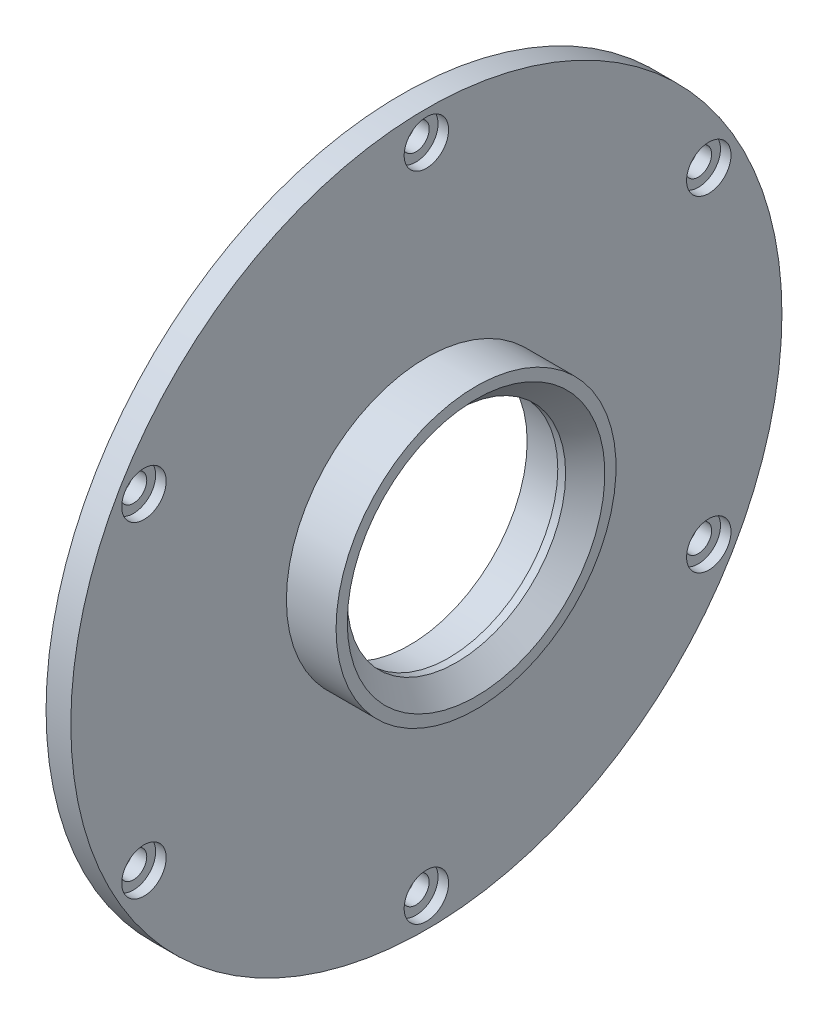
SolidWorks part; units mm, degrees
ref_plane "Front Plane" through (0, 0, 0) normal (0, 0, 1) x (1, 0, 0)
ref_plane "Top Plane" through (0, 0, 0) normal (0, 1, 0) x (1, 0, 0)
ref_plane "Right Plane" through (0, 0, 0) normal (1, 0, 0) x (0, 0, -1)
sketch "Sketch2" plane through (0, 0, 0) normal (0, 0, 1) x (1, 0, 0)
  line L0 (0, 0) -> (58.591, 0) construction
  line L2 (0, 0) -> (18.4, 0)
  line L3 (0, 0) -> (0, 2.5)
  line L4 (0, 2.5) -> (18.4, 2.5)
  line L5 (18.4, 0) -> (18.4, 2.5)
  line L6 (6, 2.5) -> (6, 6)
  line L11 (6, 6) -> (9.97, 6)
  line L16 (12.97, 6) -> (12.97, 3)
  line L17 (12.97, 3) -> (13.6304, 3)
  line L18 (13.6304, 3) -> (13.6304, 2.5)
  line L19 (13.6304, 2.5) -> (6, 2.5)
  line L22 (13.6304, 2.5) -> (16.1104, 2.5)
  line L23 (13.6304, 2.5) -> (13.6304, 4)
  line L24 (13.6304, 4) -> (16.1104, 4)
  line L25 (16.1104, 2.5) -> (16.1104, 4)
  line L27 (6, 6) -> (9.97, 6)
  line L28 (6, 6) -> (6, 9)
  line L29 (6, 9) -> (9.97, 9)
  line L30 (9.97, 6) -> (9.97, 9)
  line L31 (6, 9) -> (6, 8.25)
  line L32 (6, 8.25) -> (5, 8.25)
  line L33 (8.58, 22.001) -> (8.58, 12.476) construction
  line L34 (5, 12.476) -> (12.16, 12.476)
  line L35 (9.97, 9) -> (12.16, 9)
  line L36 (5, 7.5) -> (3, 7.5)
  line L37 (5, 8.25) -> (5, 12.476)
  line L38 (5, 7.5) -> (5, 14)
  line L39 (5, 14) -> (3, 14)
  line L40 (3, 7.5) -> (3, 14)
  line L41 (5, 22.001) -> (12.16, 22.001)
  line L42 (5, 22.001) -> (5, 30.1625)
  line L43 (5, 30.1625) -> (12.16, 30.1625)
  line L44 (12.16, 22.001) -> (12.16, 30.1625)
  line L49 (16.6304, 22.001) -> (16.6304, 7.5)
  line L51 (23.0104, 7.5) -> (23.0104, 6.5)
  line L54 (16.1104, 4) -> (13.6304, 4)
  line L56 (18.0304, 7.5) -> (23.0104, 7.5)
  line L57 (13.16, 22.001) -> (16.6304, 22.001)
  line L58 (16.1104, 3.5) -> (20.0104, 3.5)
  line L59 (29.9004, 14) -> (26.9004, 11)
  line L60 (4, 31.75) -> (18.0304, 31.75)
  line L61 (18.0304, 7.5) -> (23.0104, 7.5)
  line L62 (18.0304, 7.5) -> (18.0304, 12)
  line L63 (18.0304, 12) -> (23.0104, 12)
  line L64 (23.0104, 7.5) -> (23.0104, 12)
  line L65 (18.0304, 31.75) -> (18.0304, 12)
  line L66 (23.0104, 11) -> (26.9004, 11)
  line L67 (34.8004, 23) -> (31.3004, 19.5)
  line L68 (35.8004, 31) -> (38.7904, 33.99)
  line L69 (29.9004, 14) -> (29.9004, 15)
  line L70 (29.9004, 15) -> (22.9304, 15)
  line L71 (22.9304, 15) -> (21.0304, 15)
  line L72 (18.0304, 7.5) -> (16.6304, 7.5)
  line L73 (21.0304, 15) -> (21.0304, 43)
  line L74 (20.0304, 40) -> (10.0704, 40)
  line L75 (10.0704, 40) -> (4, 40)
  line L76 (21.0304, 43) -> (20.0304, 43)
  line L77 (22.9304, 15) -> (29.9004, 15)
  line L78 (22.9304, 15) -> (22.9304, 21)
  line L79 (22.9304, 21) -> (29.9004, 21)
  line L80 (29.9004, 15) -> (29.9004, 21)
  line L81 (10.0704, 40) -> (20.0304, 40)
  line L82 (10.0704, 40) -> (10.0704, 50)
  line L83 (10.0704, 50) -> (20.0304, 50)
  line L84 (20.0304, 40) -> (20.0304, 50)
  line L85 (4, 40) -> (4, 31.75)
  line L86 (12.97, 3) -> (12.97, 2.5)
  line L87 (31.3004, 19.5) -> (29.9004, 19.5)
  line L88 (21.51, 63.5) -> (21.51, 44)
  line L89 (21.51, 63.5) -> (25.9304, 63.5)
  line L90 (25.9304, 63.5) -> (25.9304, 25)
  line L91 (27.8304, 25) -> (25.9304, 25)
  line L92 (10.0704, 48) -> (9, 48)
  line L93 (9, 48) -> (9, 53.476)
  line L94 (9, 53.476) -> (20.0304, 53.476)
  line L95 (20.0304, 53.476) -> (20.0304, 50)
  line L96 (14.5152, 63.001) -> (14.5152, 53.476) construction
  line L97 (9, 63.001) -> (20.0304, 63.001)
  line L98 (9, 63.001) -> (9, 68.2625)
  line L99 (9, 68.2625) -> (20.0304, 68.2625)
  line L100 (20.0304, 63.001) -> (20.0304, 68.2625)
  line L101 (12.97, 6) -> (11.97, 6)
  line L102 (9, 42.5) -> (5, 42.5)
  line L103 (9, 42.5) -> (9, 55)
  line L104 (9, 55) -> (5, 55)
  line L105 (5, 42.5) -> (5, 55)
  line L106 (9.97, 6) -> (10.87, 6)
  line L107 (27.8304, 25) -> (34.8004, 25)
  line L108 (34.8004, 25) -> (34.8004, 23)
  line L109 (0, 0) -> (-2, 0)
  line L110 (0, 0) -> (0, 11)
  line L111 (27.8304, 25) -> (34.8004, 25)
  line L112 (27.8304, 25) -> (27.8304, 32.5)
  line L113 (27.8304, 32.5) -> (34.8004, 32.5)
  line L114 (34.8004, 25) -> (34.8004, 32.5)
  line L115 (35.8004, 31) -> (34.8004, 31)
  line L116 (27.8304, 32.5) -> (27.8304, 64.5)
  line L117 (21.1827, 74.025) -> (6.8477, 74.025)
  line L118 (6.8477, 74.025) -> (6.8477, 76.2)
  line L119 (38.7904, 47.29) -> (30.8304, 55.25)
  line L120 (0, 11) -> (-2, 11)
  line L121 (38.7904, 43.815) -> (30.8529, 43.815)
  line L123 (-4.8, 69.85) -> (1.55, 76.2)
  line L124 (38.7904, 47.29) -> (38.7904, 33.99)
  line L125 (-2, 0) -> (-2, 11)
  line L126 (38.7904, 37.465) -> (30.8529, 37.465)
  line L127 (30.8529, 43.815) -> (30.8529, 37.465)
  line L128 (6, 2.5) -> (6, 0)
  line L129 (0, 63.5) -> (0, 30)
  line L132 (5, 63.5) -> (0, 63.5)
  line L136 (-1.8, 30) -> (-11.76, 30)
  line L138 (-13.76, 25.4) -> (-2, 25.4)
  line L139 (-2, 25.4) -> (-2, 11.5)
  line L140 (27.8304, 64.5) -> (21.1827, 64.5)
  line L141 (-1.8, 30) -> (-11.76, 30)
  line L142 (-1.8, 30) -> (-1.8, 39)
  line L143 (-1.8, 39) -> (-11.76, 39)
  line L144 (-11.76, 30) -> (-11.76, 39)
  line L145 (21.1827, 64.5) -> (21.1827, 74.025)
  line L146 (-12.76, 37) -> (-12.76, 47.29)
  line L147 (-12.76, 37) -> (-11.76, 37)
  line L148 (30.8304, 55.25) -> (30.8304, 76.2)
  line L149 (11.97, 6) -> (11.97, 5.45)
  line L154 (-2, 11.5) -> (1, 11.5)
  line L155 (5, 60.6197) -> (24.05, 60.6197)
  line L160 (5, 60.6197) -> (5, 55.8572)
  line L161 (5, 55.8572) -> (24.05, 55.8572)
  line L166 (24.05, 60.6197) -> (24.05, 55.8572)
  line L167 (5, 60.6197) -> (24.05, 55.8572) construction
  line L172 (5, 55.8572) -> (24.05, 60.6197) construction
  line L173 (24.05, 62.2072) -> (25.9304, 62.2072)
  line L174 (11.97, 5.45) -> (10.87, 5.45)
  line L175 (10.87, 6) -> (10.87, 5.45)
  line L176 (24.05, 62.2072) -> (24.05, 54.2697)
  line L177 (24.05, 54.2697) -> (25.9304, 54.2697)
  line L178 (25.9304, 62.2072) -> (25.9304, 54.2697)
  line L179 (24.05, 62.2072) -> (25.9304, 54.2697) construction
  line L180 (24.05, 54.2697) -> (25.9304, 62.2072) construction
  line L181 (3, 19.6197) -> (15.7, 19.6197)
  line L182 (3, 19.6197) -> (3, 14.8572)
  line L183 (3, 14.8572) -> (15.7, 14.8572)
  line L184 (15.7, 19.6197) -> (15.7, 14.8572)
  line L185 (3, 19.6197) -> (15.7, 14.8572) construction
  line L186 (3, 14.8572) -> (15.7, 19.6197) construction
  line L187 (15.7, 21.2072) -> (16.6304, 21.2072)
  line L188 (15.7, 21.2072) -> (15.7, 13.2697)
  line L189 (15.7, 13.2697) -> (16.6304, 13.2697)
  line L190 (16.6304, 21.2072) -> (16.6304, 13.2697)
  line L191 (15.7, 21.2072) -> (16.6304, 13.2697) construction
  line L192 (15.7, 13.2697) -> (16.6304, 21.2072) construction
  line L193 (1, 11.5) -> (1, 6.5)
  line L194 (1, 6.5) -> (3, 6.5)
  line L195 (23.0104, 6.5) -> (20.0104, 3.5)
  line L196 (5, 63.5) -> (5, 42.5)
  line L197 (5, 42.5) -> (3, 42.5)
  line L198 (3, 42.5) -> (3, 6.5)
  line L199 (6, 0) -> (12.97, 0)
  line L200 (12.97, 0) -> (12.97, 2.5)
  line L201 (18.0304, 31.75) -> (18.0304, 35.875)
  line L202 (18.0304, 35.875) -> (21.0304, 35.875)
  line L203 (30.8304, 76.2) -> (6.8477, 76.2)
  line L204 (3.4027, 69.85) -> (7.8477, 69.85) construction
  line L205 (7.8477, 67.4687) -> (26.8977, 67.4688)
  line L206 (7.8477, 74.025) -> (7.8477, 64.5)
  line L207 (7.8477, 64.5) -> (-1.8, 64.5)
  line L208 (-1.8, 64.5) -> (-1.8, 39)
  line L209 (-12.76, 47.29) -> (-4.8, 55.25)
  line L210 (-4.8, 55.25) -> (-4.8, 69.85)
  line L211 (7.8477, 67.4687) -> (7.8477, 72.2313)
  line L212 (7.8477, 72.2313) -> (26.8977, 72.2313)
  line L213 (26.8977, 67.4688) -> (26.8977, 72.2313)
  line L214 (26.8977, 73.8187) -> (30.8304, 73.8187)
  line L215 (26.8977, 73.8187) -> (26.8977, 65.8813)
  line L216 (26.8977, 65.8813) -> (30.8304, 65.8813)
  line L217 (30.8304, 73.8187) -> (30.8304, 65.8813)
  line L218 (3.4027, 72.2313) -> (25.6277, 72.2313)
  line L219 (3.4027, 72.2313) -> (3.4027, 67.4687)
  line L220 (3.4027, 67.4687) -> (25.6277, 67.4687)
  line L221 (25.6277, 72.2313) -> (25.6277, 67.4687)
  line L222 (25.6277, 69.85) -> (21.1827, 69.85) construction
  line L223 (21.51, 44) -> (22.9304, 44)
  line L224 (22.9304, 44) -> (22.9304, 21)
  line L225 (13.6304, 4) -> (13.6304, 12.2697)
  line L226 (13.6304, 12.2697) -> (13.16, 12.2697)
  line L227 (13.16, 12.2697) -> (13.16, 22.001)
  line L228 (12.16, 9) -> (12.16, 12.476)
  line L229 (-1.8, 30) -> (0, 30)
  line L230 (9, 65.6317) -> (3.4027, 65.6317) construction
  line L231 (20.0304, 65.6317) -> (25.6277, 65.6317) construction
  line L232 (1.55, 76.2) -> (6.8477, 76.2)
  line L233 (-11.76, 30) -> (-13.76, 30)
  line L234 (-13.76, 30) -> (-13.76, 25.4)
  circle A0 centre (26.8804, 25.95) radius 0.95
  circle A1 centre (21.9804, 15.95) radius 0.95
  circle A2 centre (17.3304, 8.2) radius 0.7
  circle A3 centre (10.42, 6.45) radius 0.45
  circle A4 centre (-0.9, 30.9) radius 0.9
  point P7 (24.9902, 58.2385)
  point P131 (16.1652, 17.2385)
  point P135 (14.525, 58.2385)
  point P146 (9.35, 17.2385)
sketch "Sketch3" plane through (0, 0, 0) normal (0, 0, 1) x (1, 0, 0)
  line L0 (34.8004, 25) -> (34.8004, 23) construction
  line L4 (29.9004, 15) -> (29.9004, 21) construction
  line L5 (31.3004, 19.5) -> (29.9004, 19.5) construction
  line L6 (34.8004, 23) -> (31.3004, 19.5) construction
  line L7 (22.9304, 21) -> (29.9004, 21) construction
  line L11 (34.8004, 25) -> (34.8004, 23)
  line L15 (29.9004, 19.5) -> (29.9004, 21)
  line L16 (31.3004, 19.5) -> (29.9004, 19.5)
  line L17 (34.8004, 23) -> (31.3004, 19.5)
  line L18 (22.9304, 21) -> (29.9004, 21)
  line L22 (27.8304, 25) -> (25.9304, 25) construction
  line L23 (27.8304, 25) -> (34.8004, 25) construction
  line L24 (25.9304, 63.5) -> (25.9304, 25) construction
  line L25 (22.9304, 44) -> (22.9304, 21) construction
  line L26 (21.51, 44) -> (22.9304, 44) construction
  line L27 (21.51, 63.5) -> (21.51, 44) construction
  line L28 (21.51, 63.5) -> (25.9304, 63.5) construction
  line L29 (27.8304, 25) -> (25.9304, 25)
  line L30 (27.8304, 25) -> (34.8004, 25)
  line L31 (25.9304, 63.5) -> (25.9304, 25)
  line L32 (22.9304, 44) -> (22.9304, 21)
  line L33 (21.51, 44) -> (22.9304, 44)
  line L34 (21.51, 63.5) -> (21.51, 44)
  line L35 (21.51, 63.5) -> (25.9304, 63.5)
revolve "Revolve1" add sketch "Sketch3" angle 360 about L0
sketch "Sketch4" plane through (0, 0, 0) normal (1, 0, 0) x (0, 0, -1)
  line L0 (0, 0) -> (0, 69.85) construction
  line L1 (0, 0) -> (13.6271, 68.5079) construction
  line L2 (0, 0) -> (0, 58.2385) construction
  line L3 (0, 0) -> (50.436, 29.1192) construction
  line L4 (0, 0) -> (0, 31.75) construction
  line L5 (0, 0) -> (12.1502, 29.3332) construction
  line L6 (0, 0) -> (0, 17.2385) construction
  line L7 (0, 0) -> (14.929, 8.6192) construction
  line L8 (0, 0) -> (0, 58.2385) construction
  line L9 (0, 0) -> (50.436, 29.1192) construction
  line L10 (0, 0) -> (5.9583, 29.9542) construction
  line L11 (0, 0) -> (16.9677, 25.394) construction
  circle A0 centre (0, 0) radius 69.85 construction
  circle A1 centre (0, 0) radius 58.2385 construction
  circle A2 centre (0, 0) radius 31.75 construction
  circle A3 centre (0, 0) radius 17.2385 construction
  circle A4 centre (0, 69.85) radius 3.175
  circle A5 centre (0, 58.2385) radius 4.7625
  circle A6 centre (0, 31.75) radius 3.175
  circle A7 centre (0, 17.2385) radius 4.7625
  circle A8 centre (13.6271, 68.5079) radius 3.175
  circle A9 centre (26.7304, 64.533) radius 3.175
  circle A10 centre (38.8066, 58.0782) radius 3.175
  circle A11 centre (49.3914, 49.3914) radius 3.175
  circle A12 centre (58.0782, 38.8066) radius 3.175
  circle A13 centre (64.533, 26.7304) radius 3.175
  circle A14 centre (68.5079, 13.6271) radius 3.175
  circle A15 centre (69.85, 0) radius 3.175
  circle A16 centre (68.5079, -13.6271) radius 3.175
  circle A17 centre (64.533, -26.7304) radius 3.175
  circle A18 centre (58.0782, -38.8066) radius 3.175
  circle A19 centre (49.3914, -49.3914) radius 3.175
  circle A20 centre (38.8066, -58.0782) radius 3.175
  circle A21 centre (26.7304, -64.533) radius 3.175
  circle A22 centre (13.6271, -68.5079) radius 3.175
  circle A23 centre (0, -69.85) radius 3.175
  circle A24 centre (-13.6271, -68.5079) radius 3.175
  circle A25 centre (-26.7304, -64.533) radius 3.175
  circle A26 centre (-38.8066, -58.0782) radius 3.175
  circle A27 centre (-49.3914, -49.3914) radius 3.175
  circle A28 centre (-58.0782, -38.8066) radius 3.175
  circle A29 centre (-64.533, -26.7304) radius 3.175
  circle A30 centre (-68.5079, -13.6271) radius 3.175
  circle A31 centre (-69.85, 0) radius 3.175
  circle A32 centre (-68.5079, 13.6271) radius 3.175
  circle A33 centre (-64.533, 26.7304) radius 3.175
  circle A34 centre (-58.0782, 38.8066) radius 3.175
  circle A35 centre (-49.3914, 49.3914) radius 3.175
  circle A36 centre (-38.8066, 58.0782) radius 3.175
  circle A37 centre (-26.7304, 64.533) radius 3.175
  circle A38 centre (-13.6271, 68.5079) radius 3.175
  circle A47 centre (50.436, 29.1192) radius 4.7625
  circle A48 centre (50.436, -29.1192) radius 4.7625
  circle A49 centre (0, -58.2385) radius 4.7625
  circle A50 centre (-50.436, -29.1192) radius 4.7625
  circle A51 centre (-50.436, 29.1192) radius 4.7625
  circle A58 centre (12.1502, 29.3332) radius 3.175
  circle A59 centre (22.4506, 22.4506) radius 3.175
  circle A60 centre (29.3332, 12.1502) radius 3.175
  circle A61 centre (31.75, 0) radius 3.175
  circle A62 centre (29.3332, -12.1502) radius 3.175
  circle A63 centre (22.4506, -22.4506) radius 3.175
  circle A64 centre (12.1502, -29.3332) radius 3.175
  circle A65 centre (0, -31.75) radius 3.175
  circle A66 centre (-12.1502, -29.3332) radius 3.175
  circle A67 centre (-22.4506, -22.4506) radius 3.175
  circle A68 centre (-29.3332, -12.1502) radius 3.175
  circle A69 centre (-31.75, 0) radius 3.175
  circle A70 centre (-29.3332, 12.1502) radius 3.175
  circle A71 centre (-22.4506, 22.4506) radius 3.175
  circle A72 centre (14.929, 8.6192) radius 4.7625
  circle A73 centre (14.929, -8.6192) radius 4.7625
  circle A74 centre (0, -17.2385) radius 4.7625
  circle A75 centre (-14.929, -8.6192) radius 4.7625
  circle A76 centre (-14.929, 8.6192) radius 4.7625
  circle A77 centre (0, 0) radius 50
  circle A78 centre (0, 0) radius 9
  circle A79 centre (-12.1502, 29.3332) radius 3.175
  circle A80 centre (0, 0) radius 76.2
  circle A81 centre (0, 0) radius 74.025
  circle A82 centre (0, 69.85) radius 3.9687
  circle A83 centre (49.3914, 49.3914) radius 3.9687
  circle A84 centre (69.85, 0) radius 3.9688
  circle A85 centre (49.3914, -49.3914) radius 3.9687
  circle A86 centre (0, -69.85) radius 3.9687
  circle A87 centre (-49.3914, -49.3914) radius 3.9687
  circle A88 centre (-69.85, 0) radius 3.9688
  circle A89 centre (-49.3914, 49.3914) radius 3.9687
  circle A90 centre (0, 69.85) radius 2.3812
  circle A91 centre (13.6271, 68.5079) radius 2.3812
  circle A92 centre (26.7304, 64.533) radius 2.3813
  circle A93 centre (38.8066, 58.0782) radius 2.3812
  circle A94 centre (49.3914, 49.3914) radius 2.3812
  circle A95 centre (58.0782, 38.8066) radius 2.3812
  circle A96 centre (64.533, 26.7304) radius 2.3813
  circle A97 centre (68.5079, 13.6271) radius 2.3813
  circle A98 centre (69.85, 0) radius 2.3813
  circle A99 centre (68.5079, -13.6271) radius 2.3813
  circle A100 centre (64.533, -26.7304) radius 2.3813
  circle A101 centre (58.0782, -38.8066) radius 2.3812
  circle A102 centre (49.3914, -49.3914) radius 2.3812
  circle A103 centre (38.8066, -58.0782) radius 2.3812
  circle A104 centre (26.7304, -64.533) radius 2.3813
  circle A105 centre (13.6271, -68.5079) radius 2.3812
  circle A106 centre (0, -69.85) radius 2.3812
  circle A107 centre (-13.6271, -68.5079) radius 2.3812
  circle A108 centre (-26.7304, -64.533) radius 2.3813
  circle A109 centre (-38.8066, -58.0782) radius 2.3812
  circle A110 centre (-49.3914, -49.3914) radius 2.3812
  circle A111 centre (-58.0782, -38.8066) radius 2.3812
  circle A112 centre (-64.533, -26.7304) radius 2.3812
  arc A113 (3.0399, 30.8338) -> (8.9911, 29.65) centre (5.9583, 29.9542) cw
  arc A114 (14.6081, 27.3234) -> (19.6532, 23.9523) centre (16.9677, 25.394) cw
  arc A115 (23.9523, 19.6532) -> (27.3234, 14.6081) centre (25.394, 16.9677) cw
  arc A116 (29.65, 8.9911) -> (30.8338, 3.0399) centre (29.9542, 5.9583) cw
  arc A117 (30.8338, -3.0399) -> (29.65, -8.9911) centre (29.9542, -5.9583) cw
  arc A118 (27.3234, -14.6081) -> (23.9523, -19.6532) centre (25.394, -16.9677) cw
  arc A119 (19.6532, -23.9523) -> (14.6081, -27.3234) centre (16.9677, -25.394) cw
  arc A120 (8.9911, -29.65) -> (3.0399, -30.8338) centre (5.9583, -29.9542) cw
  arc A121 (-3.0399, -30.8338) -> (-8.9911, -29.65) centre (-5.9583, -29.9542) cw
  arc A122 (-14.6081, -27.3234) -> (-19.6532, -23.9523) centre (-16.9677, -25.394) cw
  arc A123 (-23.9523, -19.6532) -> (-27.3234, -14.6081) centre (-25.394, -16.9677) cw
  arc A124 (-29.65, -8.9911) -> (-30.8338, -3.0399) centre (-29.9542, -5.9583) cw
  arc A125 (-30.8338, 3.0399) -> (-29.65, 8.9911) centre (-29.9542, 5.9583) cw
  arc A126 (-27.3234, 14.6081) -> (-23.9523, 19.6532) centre (-25.394, 16.9677) cw
  arc A127 (-19.6532, 23.9523) -> (-14.6081, 27.3234) centre (-16.9677, 25.394) cw
  arc A128 (-8.9911, 29.65) -> (-3.0399, 30.8338) centre (-5.9583, 29.9542) cw
  arc A129 (26.9875, 0) -> (26.9932, 0.1932) centre (30.2705, 0) cw
  arc A130 (65.0988, 0.2771) -> (65.0875, 0) centre (68.4964, 0) ccw
  circle A131 centre (1.5875, 0) radius 40
  circle A132 centre (1.5875, 0) radius 2.5
  circle A133 centre (1.5875, 0) radius 3
  circle A134 centre (1.5875, 0) radius 43
  circle A135 centre (-68.5079, -13.6271) radius 2.3813
  circle A136 centre (-69.85, 0) radius 2.3813
  circle A137 centre (-68.5079, 13.6271) radius 2.3813
  circle A138 centre (-64.533, 26.7304) radius 2.3812
  circle A139 centre (-58.0782, 38.8066) radius 2.3812
  circle A140 centre (-49.3914, 49.3914) radius 2.3812
  circle A141 centre (-38.8066, 58.0782) radius 2.3812
  circle A142 centre (-26.7304, 64.533) radius 2.3813
  circle A143 centre (-13.6271, 68.5079) radius 2.3812
  circle A144 centre (0, 58.2385) radius 2.3812
  circle A145 centre (0, 58.2385) radius 3.9688
  circle A146 centre (50.436, 29.1192) radius 3.9688
  circle A147 centre (50.436, 29.1192) radius 2.3813
  circle A148 centre (50.436, -29.1192) radius 3.9687
  circle A149 centre (50.436, -29.1192) radius 2.3812
  circle A150 centre (0, -58.2385) radius 3.9687
  circle A151 centre (0, -58.2385) radius 2.3812
  circle A152 centre (-50.436, -29.1192) radius 3.9687
  circle A153 centre (-50.436, -29.1192) radius 2.3812
  circle A154 centre (-50.436, 29.1192) radius 3.9687
  circle A155 centre (-50.436, 29.1192) radius 2.3812
  spline S1 degree 4 poles (26.9875, 0) (26.9875, -0.0248) (26.9882, -0.0743) (26.9912, -0.1613) (26.9992, -0.2849) (27.0142, -0.4323) (27.0403, -0.5994) (27.0821, -0.7965) (27.1455, -1.0177) (27.2241, -1.2336) (27.3173, -1.4437) (27.4329, -1.6623) (27.5739, -1.8864) (27.7427, -2.1125) (27.9417, -2.3365) (28.1305, -2.5184) (28.3007, -2.6647) (28.4457, -2.7828) (28.5617, -2.8775) (28.6745, -2.9758) (28.7813, -3.0807) (28.9057, -3.2206) (29.0482, -3.4108) (29.197, -3.6576) (29.3758, -4.0447) (29.5291, -4.5502) (29.6152, -5.1612) (29.5933, -5.8758) (29.4507, -6.5869) (29.186, -7.2733) (28.8461, -7.831) (28.4818, -8.2549) (28.1375, -8.5536) (27.8792, -8.7284) (27.6484, -8.8496) (27.4154, -8.9438) (27.2144, -9.0029) (27.0118, -9.0554) (26.7709, -9.1263) (26.5334, -9.2082) (26.2634, -9.3231) (25.9685, -9.4827) (25.5538, -9.7623) (25.0678, -10.2216) (24.6281, -10.8948) (24.3613, -11.7878) (24.3459, -12.6097) (24.4764, -13.2366) (24.6525, -13.7006) (24.8058, -14.0202) (24.9382, -14.271) (25.0503, -14.5321) (25.1258, -14.8064) (25.1736, -15.0995) (25.1911, -15.4094) (25.1742, -15.8163) (25.0891, -16.3148) (24.907, -16.8764) (24.5182, -17.6315) (23.9757, -18.2942) (23.3695, -18.7764) (22.7564, -19.084) (22.3641, -19.2199) (22.0554, -19.2923) (21.7533, -19.3289) (21.4612, -19.3296) (21.1723, -19.2896) (20.8852, -19.2417) (20.5956, -19.2104) (20.3043, -19.1994) (19.8669, -19.2177) (19.2899, -19.3231) (18.5833, -19.6092) (17.8444, -20.1834) (17.3807, -20.828) (17.1316, -21.424) (17.0182, -21.8879) (16.9714, -22.1971) (16.9537, -22.4701) (16.9533, -22.7044) (16.9619, -22.9384) (16.9737, -23.1333) (16.977, -23.3286) (16.9594, -23.5624) (16.9177, -23.8101) (16.834, -24.1055) (16.6578, -24.5276) (16.3623, -25.0151) (15.9278, -25.5198) (15.3432, -25.99) (14.6957, -26.3472) (14.0068, -26.5857) (13.3856, -26.6851) (12.847, -26.6849) (12.4166, -26.6224) (12.1324, -26.5468) (11.9058, -26.4598) (11.7342, -26.3753) (11.6017, -26.2989) (11.4727, -26.2169) (11.3444, -26.1337) (11.1825, -26.0322) (10.9836, -25.9179) (10.7435, -25.7991) (10.4587, -25.6867) (10.0106, -25.5536) (9.3843, -25.468) (8.599, -25.5363) (7.7243, -25.8773) (7.1093, -26.3459) (6.716, -26.8042) (6.4745, -27.1841) (6.3352, -27.4489) (6.215, -27.7227) (6.1113, -28.0028) (5.9959, -28.2789) (5.841, -28.5357) (5.6522, -28.7792) (5.4316, -29.007) (5.1188, -29.2711) (4.6965, -29.5439) (4.1624, -29.7882) (3.5487, -29.9564) (2.9521, -30.0296) (2.386, -30.0225) (1.8595, -29.949) (1.3409, -29.8055) (0.9058, -29.6147) (0.5544, -29.4004) (0.2828, -29.1832) (0.0847, -28.9875) (-0.0865, -28.768) (-0.2353, -28.5332) (-0.3904, -28.3016) (-0.5598, -28.0786) (-0.792, -27.8146) (-1.1036, -27.5274) (-1.5105, -27.2448) (-2.0688, -26.9834) (-2.7167, -26.8202) (-3.459, -26.7949) (-4.1529, -26.9407) (-4.7224, -27.1899) (-5.1296, -27.455) (-5.3866, -27.661) (-5.5925, -27.8507) (-5.7558, -28.014) (-5.9199, -28.1766) (-6.0977, -28.3246) (-6.3382, -28.4851) (-6.6906, -28.6628) (-7.1669, -28.8182) (-7.7668, -28.9076) (-8.4201, -28.8957) (-9.0747, -28.7804) (-9.7144, -28.5614) (-10.3217, -28.2381) (-10.8061, -27.8636) (-11.1671, -27.4837) (-11.4143, -27.1402) (-11.5734, -26.859) (-11.6946, -26.573) (-11.7735, -26.2857) (-11.8173, -25.9915) (-11.8668, -25.6988) (-11.9353, -25.4093) (-12.0257, -25.1261) (-12.198, -24.7091) (-12.5089, -24.187) (-13.0379, -23.6191) (-13.8448, -23.1355) (-14.6072, -22.9365) (-15.2369, -22.9149) (-15.701, -22.9694) (-16.0024, -23.0316) (-16.2609, -23.107) (-16.4782, -23.1841) (-16.6576, -23.2529) (-16.8015, -23.307) (-16.9839, -23.3672) (-17.2087, -23.4203) (-17.4853, -23.4534) (-17.811, -23.4543) (-18.2291, -23.4104) (-18.7305, -23.2885) (-19.2884, -23.06) (-19.8603, -22.7052) (-20.3581, -22.2764) (-20.7758, -21.7899) (-21.1086, -21.2598) (-21.3336, -20.7318) (-21.4619, -20.2263) (-21.5006, -19.8113) (-21.4889, -19.4989) (-21.4468, -19.2424) (-21.3965, -19.0408) (-21.34, -18.8332) (-21.2878, -18.6168) (-21.2341, -18.3322) (-21.1962, -17.9773) (-21.1985, -17.5604) (-21.2781, -17.0173) (-21.4721, -16.4256) (-21.838, -15.7861) (-22.3482, -15.2578) (-22.8946, -14.8957) (-23.3828, -14.6878) (-23.7368, -14.5834) (-24.0536, -14.5215) (-24.3285, -14.4876) (-24.6045, -14.47) (-24.8811, -14.458) (-25.1556, -14.4184) (-25.4228, -14.3439) (-25.6932, -14.2375) (-26.1109, -14.0218) (-26.5677, -13.6822) (-27.0258, -13.1981) (-27.4314, -12.5682) (-27.7017, -11.9578) (-27.8746, -11.3112) (-27.9332, -10.727) (-27.9111, -10.2247) (-27.8415, -9.8214) (-27.7568, -9.5159) (-27.6427, -9.2298) (-27.5004, -8.9659) (-27.3212, -8.7261) (-27.1301, -8.4966) (-26.9071, -8.1967) (-26.6417, -7.7583) (-26.3997, -7.1508) (-26.2841, -6.3875) (-26.3642, -5.5798) (-26.6019, -4.9055) (-26.9193, -4.3761) (-27.2736, -3.9636) (-27.583, -3.6904) (-27.8719, -3.4871) (-28.1186, -3.3407) (-28.3135, -3.2371) (-28.5043, -3.1411) (-28.6854, -3.0419) (-28.9002, -2.8984) (-29.1355, -2.6958) (-29.4123, -2.3882) (-29.6958, -1.9552) (-29.932, -1.437) (-30.0985, -0.839) (-30.1779, -0.2025) (-30.1603, 0.4599) (-30.0348, 1.1323) (-29.8199, 1.711) (-29.5617, 2.1719) (-29.3035, 2.5118) (-29.0784, 2.748) (-28.8655, 2.924) (-28.6761, 3.0468) (-28.5112, 3.1367) (-28.3775, 3.205) (-28.2106, 3.2911) (-28.0136, 3.4005) (-27.7912, 3.5413) (-27.5508, 3.7219) (-27.2011, 4.0343) (-26.7941, 4.5285) (-26.4419, 5.234) (-26.2777, 6.1494) (-26.351, 6.9081) (-26.5268, 7.4739) (-26.7218, 7.8823) (-26.8619, 8.1196) (-26.9953, 8.3144) (-27.1373, 8.5028) (-27.2613, 8.6553) (-27.3845, 8.8088) (-27.518, 9.0035) (-27.6324, 9.2103) (-27.7412, 9.4693) (-27.8326, 9.7814) (-27.9074, 10.1885) (-27.9345, 10.6913) (-27.8808, 11.2771) (-27.6878, 12.0229) (-27.3166, 12.8111) (-26.8405, 13.4278) (-26.3243, 13.8718) (-25.9118, 14.1263) (-25.6503, 14.2566) (-25.3769, 14.3596) (-25.0933, 14.4318) (-24.8027, 14.4634) (-24.5112, 14.4738) (-24.1629, 14.5033) (-23.7608, 14.5717) (-23.1887, 14.7443) (-22.5511, 15.0901) (-21.962, 15.6231) (-21.544, 16.2749) (-21.3217, 16.857) (-21.2175, 17.3851) (-21.1902, 17.8397) (-21.2185, 18.2374) (-21.2771, 18.5739) (-21.3443, 18.8506) (-21.405, 19.0706) (-21.4579, 19.2928) (-21.4883, 19.5194) (-21.4981, 19.805) (-21.4664, 20.1907) (-21.3565, 20.6672) (-21.1331, 21.2135) (-20.8025, 21.7541) (-20.3882, 22.2461) (-19.8974, 22.677) (-19.3379, 23.033) (-18.7964, 23.2649) (-18.309, 23.3941) (-17.8981, 23.4483) (-17.5726, 23.4572) (-17.2924, 23.4331) (-17.0602, 23.3874) (-16.8337, 23.3199) (-16.6495, 23.2499) (-16.4659, 23.1791) (-16.2424, 23.1025) (-16.0156, 23.0362) (-15.7461, 22.9768) (-15.2967, 22.9185) (-14.7035, 22.9278) (-13.9592, 23.0948) (-13.1407, 23.5365) (-12.5805, 24.0908) (-12.2382, 24.6309) (-12.0505, 25.0599) (-11.9538, 25.3442) (-11.8892, 25.5989) (-11.8463, 25.8198) (-11.8162, 26.0048) (-11.7926, 26.153) (-11.7577, 26.3372) (-11.6989, 26.5548) (-11.5969, 26.8111) (-11.4414, 27.0975) (-11.1977, 27.4473) (-10.8392, 27.8343) (-10.3554, 28.2166) (-9.7549, 28.5431) (-9.1303, 28.7642) (-8.5, 28.8851) (-7.879, 28.911) (-7.3126, 28.8458) (-6.8128, 28.7091) (-6.4345, 28.54) (-6.1692, 28.378) (-5.9665, 28.2173) (-5.8163, 28.0752) (-5.6659, 27.9232) (-5.5067, 27.7699) (-5.2907, 27.5806) (-5.0072, 27.369) (-4.6509, 27.1597) (-4.148, 26.9513) (-3.5452, 26.8146) (-2.8302, 26.7991) (-2.0381, 26.9749) (-1.3495, 27.3225) (-0.8483, 27.741) (-0.5146, 28.1291) (-0.2991, 28.4338) (-0.1401, 28.6862) (0.0331, 28.93) (0.2405, 29.146) (0.4774, 29.3422) (0.7418, 29.5165) (1.1036, 29.7066) (1.5741, 29.882) (2.1471, 30.006) (2.8151, 30.041) (3.4791, 29.9721) (4.2039, 29.7804) (4.8064, 29.4933) (5.2708, 29.1628) (5.6049, 28.8311) (5.7894, 28.6062) (5.9424, 28.3744) (6.0642, 28.1249) (6.161, 27.8653) (6.2635, 27.608) (6.3813, 27.357) (6.5388, 27.0748) (6.7484, 26.7704) (7.0986, 26.3707) (7.6135, 25.9641) (8.2747, 25.644) (8.9962, 25.4959) (9.6181, 25.496) (10.1582, 25.5894) (10.5546, 25.7168) (10.8796, 25.8629) (11.1331, 26.0022) (11.3224, 26.1188) (11.5021, 26.2366) (11.6784, 26.3463) (11.9094, 26.4649) (12.2028, 26.5718) (12.6092, 26.6624) (13.1291, 26.6958) (13.7, 26.6444) (14.3062, 26.4914) (14.8974, 26.2443) (15.459, 25.9029) (15.9732, 25.4681) (16.3631, 25.0071) (16.6337, 24.567) (16.8044, 24.1822) (16.9036, 23.8716) (16.9571, 23.5978) (16.9755, 23.3672) (16.9741, 23.1748) (16.9669, 23.0211) (16.9571, 22.8289) (16.9512, 22.5982) (16.9599, 22.3287) (16.9946, 22.0224) (17.0874, 21.5638) (17.3043, 20.9714) (17.7315, 20.3087) (18.4426, 19.693) (19.1468, 19.3677) (19.739, 19.2351) (20.1882, 19.2012) (20.4852, 19.2034) (20.7812, 19.2282) (21.0745, 19.2719) (21.3675, 19.3208) (21.6648, 19.3336) (21.9737, 19.306) (22.2899, 19.241) (22.6922, 19.1116) (23.1641, 18.8854) (23.669, 18.5404) (24.1634, 18.0628) (24.569, 17.5219) (24.8807, 16.9345) (25.0937, 16.316) (25.184, 15.7743) (25.1924, 15.3317) (25.1581, 14.9969) (25.1154, 14.7695) (25.0522, 14.5468) (24.9658, 14.3321) (24.8616, 14.1257) (24.7568, 13.9198) (24.6402, 13.6649) (24.524, 13.3562) (24.3985, 12.886) (24.3389, 12.2663) (24.4166, 11.5605) (24.6979, 10.7931) (25.0952, 10.2042) (25.5426, 9.7706) (25.9551, 9.4883) (26.2689, 9.3208) (26.5627, 9.1971) (26.83, 9.1062) (27.1019, 9.0315) (27.3749, 8.9598) (27.6385, 8.8574) (27.887, 8.7225) (28.1969, 8.5098) (28.5449, 8.1936) (28.9002, 7.7549) (29.2229, 7.1817) (29.4529, 6.562) (29.5858, 5.9108) (29.6165, 5.2432) (29.5485, 4.659) (29.4188, 4.1725) (29.2636, 3.7931) (29.1144, 3.5129) (28.9404, 3.2582) (28.7432, 3.0317) (28.5155, 2.8371) (28.281, 2.6515) (28.0578, 2.4519) (27.8492, 2.2371) (27.6347, 1.9761) (27.4574, 1.7102) (27.3152, 1.4444) (27.2047, 1.1845) (27.1307, 0.9703) (27.0789, 0.7793) (27.0441, 0.6164) (27.021, 0.472) (27.0061, 0.351) (26.9981, 0.2662) (26.9946, 0.2176) (26.9932, 0.1932) knots 0.06864 0.06864 0.06864 0.06864 0.06864 0.069106 0.069571 0.070037 0.070502 0.071433 0.072364 0.073295 0.074226 0.075157 0.076088 0.077301 0.078514 0.079727 0.08094 0.081547 0.082153 0.08276 0.083366 0.083973 0.084579 0.085792 0.087214 0.088636 0.091479 0.094323 0.097166 0.100174 0.103182 0.10619 0.107694 0.109198 0.110555 0.111234 0.111912 0.113269 0.113948 0.114626 0.115983 0.11734 0.118697 0.120055 0.12408 0.128106 0.131537 0.134967 0.137266 0.138415 0.139565 0.140714 0.141863 0.143013 0.144162 0.145524 0.146885 0.149608 0.152331 0.155054 0.160594 0.163364 0.164749 0.166134 0.167314 0.168495 0.169675 0.170855 0.172035 0.173215 0.174395 0.175575 0.179125 0.182676 0.186612 0.190548 0.191813 0.193079 0.194345 0.195611 0.196244 0.196877 0.198142 0.198775 0.199408 0.200674 0.202207 0.203741 0.206808 0.209874 0.212941 0.21584 0.218738 0.221637 0.223086 0.224535 0.225775 0.226394 0.227014 0.227634 0.228253 0.228873 0.229493 0.230732 0.231971 0.233211 0.23445 0.238303 0.242155 0.245814 0.249472 0.250683 0.251894 0.253105 0.254316 0.255527 0.256738 0.257949 0.25916 0.260514 0.261868 0.264577 0.267285 0.269993 0.272142 0.27429 0.276439 0.278588 0.280839 0.281965 0.283091 0.284217 0.285343 0.286469 0.287595 0.288737 0.289879 0.292163 0.294447 0.296732 0.299827 0.302922 0.306383 0.308113 0.309844 0.31078 0.311716 0.312652 0.313588 0.314524 0.31546 0.317332 0.319969 0.322606 0.325244 0.327881 0.330703 0.333524 0.336346 0.337757 0.339168 0.340372 0.341576 0.34278 0.343984 0.345188 0.346392 0.347596 0.3488 0.352495 0.356189 0.36002 0.36385 0.365096 0.366342 0.367588 0.368834 0.369457 0.370079 0.370702 0.371325 0.372571 0.373817 0.375207 0.376596 0.379375 0.382154 0.384933 0.387459 0.389986 0.392513 0.39504 0.396723 0.398407 0.399249 0.400091 0.400932 0.401774 0.402737 0.4037 0.405625 0.407551 0.409476 0.412569 0.415662 0.41939 0.421254 0.423119 0.42424 0.425361 0.426483 0.427604 0.428726 0.429847 0.430969 0.43209 0.433431 0.437455 0.440138 0.44282 0.445528 0.448236 0.450943 0.452297 0.453651 0.454862 0.456073 0.457284 0.458495 0.459706 0.460916 0.463338 0.466783 0.470228 0.473297 0.476366 0.478273 0.480179 0.482085 0.483038 0.483991 0.484828 0.485664 0.486501 0.487337 0.48901 0.490683 0.493189 0.495695 0.498202 0.500708 0.503552 0.506397 0.509241 0.510663 0.512085 0.513303 0.514521 0.51513 0.515738 0.516347 0.516956 0.518174 0.519391 0.520609 0.521827 0.525766 0.529706 0.533208 0.53671 0.537985 0.53926 0.540535 0.541173 0.54181 0.543085 0.543723 0.54436 0.545635 0.54691 0.548267 0.549623 0.552335 0.555047 0.55776 0.562061 0.566363 0.567545 0.568728 0.56991 0.571092 0.572275 0.573457 0.574639 0.575822 0.577939 0.580057 0.584292 0.587472 0.590653 0.592493 0.594334 0.596174 0.598014 0.59894 0.599865 0.60079 0.601715 0.60264 0.603565 0.605415 0.607973 0.610531 0.61309 0.615648 0.618364 0.62108 0.623796 0.625154 0.626512 0.627788 0.629065 0.629703 0.630341 0.631618 0.632256 0.632895 0.634171 0.635448 0.636724 0.640232 0.643739 0.647674 0.651609 0.652825 0.65404 0.655256 0.656472 0.65708 0.657688 0.658296 0.658904 0.66012 0.661336 0.662756 0.664177 0.667018 0.669858 0.672699 0.675209 0.677718 0.680227 0.682736 0.684412 0.686087 0.686924 0.687762 0.688599 0.689437 0.690391 0.691345 0.693254 0.695162 0.697071 0.700143 0.703216 0.706655 0.710095 0.712514 0.713723 0.714933 0.716142 0.717352 0.718561 0.719771 0.721123 0.722475 0.725179 0.727883 0.730587 0.733273 0.735959 0.739989 0.741332 0.742455 0.743577 0.7447 0.745823 0.746945 0.748068 0.749191 0.750314 0.752181 0.754048 0.757782 0.760871 0.763961 0.765883 0.767806 0.769729 0.77069 0.771651 0.772492 0.773333 0.774174 0.775015 0.776698 0.77838 0.780903 0.783427 0.785951 0.788475 0.791257 0.794039 0.796822 0.798213 0.799604 0.800852 0.802099 0.802723 0.803347 0.803971 0.804595 0.805842 0.80709 0.808337 0.809585 0.81342 0.817255 0.820945 0.824634 0.825837 0.827039 0.828242 0.829444 0.830647 0.831849 0.833052 0.834254 0.835663 0.837072 0.83989 0.842708 0.845526 0.848167 0.850807 0.853447 0.856087 0.857024 0.857961 0.858897 0.859834 0.860771 0.861707 0.862644 0.863581 0.865314 0.867048 0.870515 0.873613 0.876711 0.880181 0.881916 0.883651 0.884794 0.885937 0.887081 0.888224 0.889367 0.89051 0.891653 0.892797 0.895451 0.898105 0.90076 0.903414 0.906126 0.908838 0.911549 0.912905 0.914261 0.915474 0.916686 0.917899 0.919111 0.920323 0.921536 0.922748 0.923961 0.925793 0.926709 0.927625 0.928541 0.929457 0.929915 0.930373 0.930831 0.931289 0.931289 0.931289 0.931289 0.931289
  spline S3 degree 4 poles (65.0875, 0) (65.0875, -0.2085) (65.1336, -0.6093) (65.3196, -1.4523) (65.739, -2.0447) (66.242, -2.6341) (66.7299, -3.0916) (67.1731, -3.6257) (67.5219, -4.2566) (67.8399, -5.1354) (68.0042, -6.2629) (67.9043, -7.3956) (67.5534, -8.464) (67.1166, -9.2437) (66.7001, -9.7852) (66.2223, -10.2316) (65.7042, -10.5824) (65.1033, -10.9671) (64.5015, -11.4984) (63.9836, -12.2541) (63.7076, -13.0981) (63.6577, -13.8665) (63.7509, -14.5541) (63.9279, -15.1344) (64.2231, -15.7099) (64.6171, -16.2749) (64.9859, -16.8848) (65.2405, -17.5795) (65.3772, -18.3315) (65.3953, -19.1188) (65.2888, -19.9454) (65.0416, -20.7887) (64.6379, -21.6235) (64.0595, -22.4019) (63.3699, -23.0372) (62.5888, -23.4701) (61.782, -23.7464) (61.0578, -24.1183) (60.3658, -24.7064) (59.8816, -25.4078) (59.6093, -26.1527) (59.5127, -26.9191) (59.5498, -27.5888) (59.7273, -28.2781) (60.0289, -28.9687) (60.2831, -29.7025) (60.3758, -30.5026) (60.3272, -31.328) (60.135, -32.1571) (59.8183, -32.9321) (59.3945, -33.6382) (58.8781, -34.2627) (58.2824, -34.7917) (57.6299, -35.2075) (56.9378, -35.4918) (56.2305, -35.6333) (55.5425, -35.7436) (54.9192, -35.9451) (54.3784, -36.2357) (53.8226, -36.6647) (53.3379, -37.2279) (52.9635, -37.9633) (52.7754, -38.8477) (52.8002, -39.6949) (52.9662, -40.4335) (53.0501, -41.0953) (53.0299, -41.6741) (52.9556, -42.1601) (52.7999, -42.7542) (52.5204, -43.4371) (52.0123, -44.2743) (51.2999, -45.0323) (50.5074, -45.5996) (49.6888, -45.9749) (49.0001, -46.1726) (48.294, -46.2386) (47.5903, -46.2021) (46.9326, -46.2102) (46.3301, -46.3235) (45.6752, -46.561) (45.0214, -46.9572) (44.4035, -47.5835) (43.9713, -48.3909) (43.7706, -49.1822) (43.7338, -49.9181) (43.7302, -50.5816) (43.6334, -51.2608) (43.4079, -51.9357) (42.9846, -52.7556) (42.2668, -53.6506) (41.3533, -54.3599) (40.3007, -54.8365) (39.3996, -55.0391) (38.7109, -55.0871) (38.0679, -55.0221) (37.4791, -54.8813) (36.7945, -54.7238) (35.9925, -54.6786) (35.0907, -54.8522) (34.2981, -55.2648) (33.7257, -55.7777) (33.3141, -56.326) (33.0345, -56.8561) (32.8392, -57.4643) (32.7053, -58.1318) (32.5057, -58.8072) (32.1692, -59.4564) (31.7161, -60.06) (31.1587, -60.6027) (30.4857, -61.0865) (29.6999, -61.483) (28.8088, -61.7584) (27.9539, -61.8544) (27.2176, -61.8147) (26.5366, -61.6724) (25.9236, -61.4387) (25.2656, -61.0978) (24.4787, -60.8476) (23.5806, -60.7805) (22.7614, -60.9343) (22.0678, -61.2531) (21.4811, -61.6931) (21.0427, -62.1588) (20.6764, -62.7331) (20.3896, -63.397) (20.0518, -64.0821) (19.5498, -64.7169) (18.9084, -65.2751) (18.1452, -65.7332) (17.3354, -66.0496) (16.5073, -66.2302) (15.682, -66.2803) (14.8803, -66.2037) (14.123, -66.0055) (13.4387, -65.6832) (12.8489, -65.2534) (12.2838, -64.832) (11.6928, -64.5309) (11.0975, -64.3539) (10.3927, -64.2676) (9.6512, -64.3301) (8.8745, -64.5906) (8.129, -65.0794) (7.5616, -65.6798) (7.1516, -66.2974) (6.7292, -66.7997) (6.2028, -67.2551) (5.5783, -67.6475) (4.7841, -67.9788) (3.8712, -68.1707) (2.9917, -68.2056) (2.1686, -68.1094) (1.418, -67.9057) (0.729, -67.5982) (0.1198, -67.1943) (-0.3827, -66.7012) (-0.8235, -66.1827) (-1.2889, -65.7455) (-1.7902, -65.4174) (-2.4157, -65.1372) (-3.1648, -64.9658) (-4.0581, -64.9888) (-4.9311, -65.2738) (-5.6111, -65.7021) (-6.1336, -66.172) (-6.5802, -66.5811) (-7.1109, -66.9505) (-7.7364, -67.2433) (-8.6229, -67.5039) (-9.7746, -67.5983) (-10.9176, -67.4218) (-11.9796, -66.988) (-12.7475, -66.4769) (-13.2722, -65.9967) (-13.6867, -65.4503) (-14.0119, -64.8723) (-14.4007, -64.2467) (-14.9594, -63.652) (-15.7285, -63.155) (-16.5724, -62.9064) (-17.3364, -62.8765) (-18.0247, -62.9861) (-18.6068, -63.179) (-19.1862, -63.4909) (-19.784, -63.8646) (-20.4334, -64.1501) (-21.1317, -64.3118) (-22.0298, -64.3813) (-22.9982, -64.2701) (-23.9891, -63.9533) (-24.8397, -63.4681) (-25.4154, -63.007) (-25.8399, -62.5635) (-26.1408, -62.1749) (-26.4394, -61.6789) (-26.6877, -61.0599) (-26.9007, -60.3339) (-27.2894, -59.581) (-27.8821, -58.8987) (-28.6764, -58.362) (-29.5588, -58.0865) (-30.4418, -58.0554) (-31.2145, -58.2063) (-31.8698, -58.4438) (-32.557, -58.6637) (-33.3003, -58.7515) (-34.0729, -58.7048) (-34.8508, -58.5315) (-35.6055, -58.2363) (-36.3189, -57.8248) (-36.9719, -57.301) (-37.5423, -56.6697) (-37.9855, -55.9721) (-38.293, -55.2278) (-38.4273, -54.4632) (-38.4985, -53.7131) (-38.6773, -53.0244) (-38.9694, -52.4208) (-39.4251, -51.7974) (-40.0241, -51.2777) (-40.7875, -50.8987) (-41.6779, -50.7194) (-42.492, -50.745) (-43.3317, -50.8952) (-44.2251, -50.8964) (-45.1368, -50.6758) (-46.0207, -50.2762) (-46.7791, -49.7422) (-47.4046, -49.125) (-47.899, -48.4541) (-48.2653, -47.7574) (-48.5109, -47.0338) (-48.6258, -46.3032) (-48.5997, -45.5912) (-48.5294, -44.9062) (-48.55, -44.26) (-48.6763, -43.6668) (-48.9279, -43.0203) (-49.3438, -42.3723) (-49.994, -41.7677) (-50.8134, -41.3575) (-51.5975, -41.1841) (-52.3098, -41.1392) (-52.9334, -41.0842) (-53.5681, -40.9261) (-54.1954, -40.6549) (-54.9562, -40.1853) (-55.7818, -39.4216) (-56.4191, -38.48) (-56.8229, -37.4145) (-56.9716, -36.4922) (-56.973, -35.7718) (-56.8456, -35.0891) (-56.6436, -34.4482) (-56.4711, -33.7221) (-56.4502, -32.8948) (-56.649, -32.0092) (-57.1254, -31.1487) (-57.7708, -30.51) (-58.4838, -30.0886) (-59.1915, -29.8498) (-59.8427, -29.6823) (-60.4903, -29.4299) (-61.1017, -29.048) (-61.8067, -28.434) (-62.498, -27.5279) (-62.9605, -26.4892) (-63.1725, -25.385) (-63.1692, -24.4916) (-63.0682, -23.8162) (-62.8676, -23.1941) (-62.5852, -22.636) (-62.2465, -22.0084) (-61.9776, -21.2523) (-61.8906, -20.3405) (-62.058, -19.4685) (-62.3866, -18.772) (-62.8014, -18.2154) (-63.2376, -17.7934) (-63.775, -17.4329) (-64.3938, -17.1299) (-65.0127, -16.7759) (-65.5728, -16.2922) (-66.0577, -15.701) (-66.4559, -15.0213) (-66.7642, -14.2468) (-66.9575, -13.3897) (-67.0099, -12.464) (-66.8823, -11.503) (-66.5881, -10.6131) (-66.1159, -9.8554) (-65.5448, -9.2225) (-65.0917, -8.5465) (-64.7714, -7.6968) (-64.6877, -6.8487) (-64.8104, -6.065) (-65.0973, -5.3476) (-65.4544, -4.7796) (-65.9438, -4.2625) (-66.5428, -3.8049) (-67.1216, -3.2868) (-67.5915, -2.6323) (-67.9498, -1.8869) (-68.1844, -1.0686) (-68.2839, -0.2372) (-68.2562, 0.5859) (-68.1079, 1.3824) (-67.8442, 2.1339) (-67.4759, 2.814) (-67.0091, 3.3986) (-66.4598, 3.8656) (-65.9118, 4.2957) (-65.4645, 4.7738) (-65.1323, 5.2899) (-64.854, 5.9343) (-64.7029, 6.6617) (-64.7315, 7.4865) (-64.9956, 8.3514) (-65.4279, 9.0808) (-65.9316, 9.6463) (-66.3266, 10.1843) (-66.5902, 10.7002) (-66.7614, 11.1612) (-66.9138, 11.7564) (-67.0011, 12.4893) (-66.9634, 13.468) (-66.7086, 14.4765) (-66.2914, 15.3572) (-65.7582, 16.0825) (-65.2524, 16.5896) (-64.6675, 16.9902) (-64.0348, 17.2999) (-63.4636, 17.6256) (-62.9917, 18.0165) (-62.5341, 18.5414) (-62.154, 19.2046) (-61.9168, 20.0519) (-61.9299, 20.9678) (-62.1378, 21.7576) (-62.4626, 22.4193) (-62.7816, 23.0012) (-63.0271, 23.6422) (-63.1578, 24.3419) (-63.186, 25.2645) (-62.9931, 26.3956) (-62.5388, 27.4592) (-61.8502, 28.3868) (-61.1611, 29.0013) (-60.5826, 29.3776) (-59.9893, 29.6331) (-59.4065, 29.7959) (-58.7317, 29.9901) (-58.0084, 30.339) (-57.3037, 30.9276) (-56.8101, 31.6725) (-56.5578, 32.3986) (-56.4634, 33.0779) (-56.4757, 33.6773) (-56.5996, 34.3042) (-56.8066, 34.953) (-56.9602, 35.6406) (-56.9815, 36.3717) (-56.8785, 37.1197) (-56.6546, 37.865) (-56.3011, 38.615) (-55.8067, 39.3425) (-55.1614, 40.0175) (-54.361, 40.5839) (-53.4966, 40.9773) (-52.6075, 41.1366) (-51.7446, 41.1582) (-50.9354, 41.3217) (-50.1173, 41.6976) (-49.4752, 42.2292) (-49.0228, 42.8441) (-48.7227, 43.5135) (-48.5648, 44.1335) (-48.5227, 44.8135) (-48.594, 45.5334) (-48.6316, 46.2966) (-48.501, 47.0955) (-48.2113, 47.8952) (-47.7665, 48.6665) (-47.2121, 49.3364) (-46.5757, 49.8963) (-45.8787, 50.3408) (-45.1409, 50.663) (-44.3829, 50.8574) (-43.6284, 50.9082) (-42.9043, 50.8189) (-42.206, 50.7245) (-41.5433, 50.7476) (-40.937, 50.8811) (-40.2788, 51.1471) (-39.7262, 51.5171) (-39.2658, 51.9893) (-38.9131, 52.5364) (-38.7001, 53.0023) (-38.5499, 53.5113) (-38.4639, 54.0546) (-38.4035, 54.6217) (-38.285, 55.1987) (-38.0677, 55.7784) (-37.7559, 56.3461) (-37.3536, 56.8882) (-36.8608, 57.3907) (-36.292, 57.8353) (-35.653, 58.2093) (-34.9511, 58.4983) (-34.1963, 58.6846) (-33.445, 58.7504) (-32.7165, 58.6934) (-32.0379, 58.5065) (-31.4011, 58.2671) (-30.7824, 58.1104) (-30.1851, 58.0663) (-29.5022, 58.1242) (-28.8849, 58.3025) (-28.3189, 58.5985) (-27.8275, 58.9947) (-27.4878, 59.3597) (-27.1867, 59.7905) (-26.9404, 60.2842) (-26.7513, 60.8312) (-26.5595, 61.406) (-26.2751, 61.9869) (-25.8703, 62.5469) (-25.2217, 63.2054) (-24.2606, 63.8474) (-23.1756, 64.248) (-22.0367, 64.3843) (-21.1176, 64.3105) (-20.426, 64.1457) (-19.7984, 63.8696) (-19.2337, 63.5223) (-18.5906, 63.1637) (-17.814, 62.9143) (-16.9006, 62.8522) (-16.0419, 63.0435) (-15.3589, 63.3875) (-14.8097, 63.817) (-14.3938, 64.268) (-14.0381, 64.8219) (-13.6968, 65.439) (-13.2677, 66.0042) (-12.7357, 66.4849) (-11.9841, 66.982) (-11.0834, 67.3551) (-10.0633, 67.5591) (-9.0842, 67.548) (-8.3573, 67.4245) (-7.771, 67.243) (-7.3194, 67.0495) (-6.8176, 66.7612) (-6.3001, 66.3409) (-5.7617, 65.8096) (-5.0573, 65.3395) (-4.2083, 65.0299) (-3.2534, 64.9451) (-2.3479, 65.1316) (-1.5602, 65.5324) (-0.9572, 66.039) (-0.4992, 66.5647) (-0.0052, 67.091) (0.6022, 67.5289) (1.3004, 67.8634) (2.0648, 68.0897) (2.8681, 68.1981) (3.6915, 68.1846) (4.5166, 68.0438) (5.3215, 67.769) (6.0475, 67.3745) (6.6776, 66.8734) (7.1664, 66.2705) (7.5924, 65.6494) (8.0825, 65.1337) (8.6303, 64.7473) (9.3308, 64.4229) (10.1065, 64.2585) (10.958, 64.2968) (11.8239, 64.5715) (12.5238, 64.9885) (13.1854, 65.5275) (13.9659, 65.9629) (14.8703, 66.2129) (15.8374, 66.2928) (16.7598, 66.1942) (17.6064, 65.9582) (18.3641, 65.6118) (19.0225, 65.1808) (19.5884, 64.6677) (20.0436, 64.0851) (20.3665, 63.4503) (20.6373, 62.8174) (20.9684, 62.2624) (21.3662, 61.8048) (21.8993, 61.3614) (22.5769, 60.996) (23.4387, 60.7819) (24.3544, 60.8201) (25.1246, 61.0485) (25.7695, 61.3547) (26.3415, 61.6097) (26.9734, 61.7799) (27.6537, 61.8476) (28.5471, 61.8066) (29.6399, 61.5397) (30.6542, 61.0259) (31.5244, 60.2907) (32.1021, 59.5569) (32.4531, 58.9281) (32.6734, 58.2697) (32.8078, 57.6116) (33.0089, 56.8932) (33.3912, 56.1596) (33.9941, 55.4813) (34.8277, 54.9592) (35.7018, 54.7131) (36.53, 54.6899) (37.2651, 54.8241) (37.916, 54.9939) (38.6049, 55.0879) (39.3251, 55.0511) (40.2399, 54.8566) (41.2843, 54.4001) (42.1929, 53.7166) (42.9143, 52.8543) (43.3452, 52.0721) (43.5848, 51.4329) (43.7116, 50.792) (43.7359, 50.1672) (43.7441, 49.4543) (43.8752, 48.663) (44.2408, 47.8232) (44.8096, 47.1415) (45.4346, 46.6913) (46.0673, 46.4052) (46.6536, 46.2474) (47.2985, 46.1925) (47.9868, 46.2278) (48.7, 46.219) (49.4249, 46.0682) (50.1361, 45.7868) (50.8145, 45.3859) (51.4601, 44.8584) (52.0452, 44.2029) (52.5404, 43.4193) (52.8953, 42.5175) (53.0703, 41.597) (53.0258, 40.7056) (52.8338, 39.8754) (52.765, 39.0648) (52.8965, 38.1665) (53.2341, 37.384) (53.7212, 36.7578) (54.3199, 36.2691) (54.9077, 35.9453) (55.5867, 35.7301) (56.3327, 35.6205) (57.0905, 35.4488) (57.8193, 35.1048) (58.4947, 34.6271) (59.0973, 34.0254) (59.5881, 33.3468) (59.9634, 32.6138) (60.2205, 31.8456) (60.3547, 31.0608) (60.363, 30.2877) (60.2391, 29.5502) (59.9859, 28.8754) (59.7153, 28.2337) (59.5559, 27.5989) (59.5154, 26.9867) (59.5841, 26.2884) (59.8043, 25.5789) (60.2289, 24.8712) (60.8791, 24.2424) (61.611, 23.8136) (62.326, 23.5634) (62.9328, 23.285) (63.4141, 22.962) (63.7877, 22.642) (64.2101, 22.1956) (64.6425, 21.5971) (65.0848, 20.7231) (65.3517, 19.7177) (65.4145, 18.7455) (65.3007, 17.8528) (65.1049, 17.1641) (64.7884, 16.53) (64.3858, 15.9523) (64.0442, 15.3907) (63.8209, 14.8203) (63.675, 14.1396) (63.6638, 13.3754) (63.8667, 12.5192) (64.3219, 11.7243) (64.8867, 11.1339) (65.4917, 10.7124) (66.0534, 10.3584) (66.5796, 9.9173) (67.0339, 9.369) (67.5068, 8.5758) (67.8873, 7.4932) (68.0066, 6.3429) (67.855, 5.1978) (67.5512, 4.3262) (67.2284, 3.7166) (66.8341, 3.2056) (66.4039, 2.7793) (65.9959, 2.3684) (65.6608, 1.9383) (65.4055, 1.4839) (65.2226, 0.982) (65.1371, 0.5988) (65.1074, 0.3834) (65.0988, 0.2771) knots 0.070151 0.070151 0.070151 0.070151 0.070151 0.071893 0.073635 0.074839 0.076042 0.077245 0.078449 0.079818 0.081187 0.083925 0.086561 0.087879 0.089198 0.090319 0.091441 0.092563 0.093684 0.095431 0.097177 0.099043 0.099975 0.100908 0.102141 0.103374 0.104607 0.105841 0.107249 0.108657 0.110066 0.111474 0.113209 0.114943 0.116677 0.118412 0.119867 0.121323 0.122778 0.124234 0.12632 0.127363 0.128406 0.129755 0.131103 0.132451 0.1338 0.13532 0.136841 0.138361 0.139881 0.141306 0.142731 0.144156 0.14558 0.146828 0.148076 0.149324 0.150572 0.151515 0.152459 0.154345 0.155857 0.157368 0.15888 0.160391 0.161271 0.162151 0.163031 0.163911 0.16567 0.16743 0.170022 0.171318 0.172613 0.173875 0.175136 0.176397 0.177658 0.178588 0.179518 0.181379 0.183098 0.184818 0.186006 0.187193 0.188381 0.189569 0.190921 0.192274 0.194979 0.197739 0.199119 0.200498 0.201583 0.202668 0.203753 0.204837 0.20662 0.208402 0.210245 0.211167 0.212088 0.213307 0.214526 0.215744 0.216963 0.218354 0.219746 0.221137 0.222528 0.224283 0.226038 0.227793 0.22867 0.229548 0.231022 0.232497 0.233971 0.235446 0.23742 0.238408 0.239395 0.240689 0.241984 0.243279 0.244573 0.246164 0.247754 0.249345 0.250935 0.252375 0.253816 0.255256 0.256696 0.257959 0.259221 0.260484 0.261746 0.2627 0.263654 0.265562 0.267037 0.268512 0.269987 0.271463 0.27234 0.273218 0.274973 0.276729 0.278484 0.279875 0.281266 0.282657 0.284048 0.285266 0.286484 0.287703 0.288921 0.289842 0.290763 0.292606 0.294388 0.296171 0.297257 0.298342 0.299427 0.300512 0.301893 0.303273 0.306034 0.308738 0.31009 0.311442 0.312629 0.313816 0.315004 0.316191 0.31791 0.319629 0.32149 0.32242 0.323351 0.324612 0.325874 0.327136 0.328398 0.329694 0.33099 0.333582 0.335342 0.337101 0.33798 0.33886 0.339739 0.340619 0.34213 0.343641 0.345152 0.346663 0.34855 0.350437 0.351686 0.352934 0.354182 0.355431 0.356856 0.358281 0.359706 0.361131 0.362651 0.364171 0.365691 0.367211 0.368559 0.369907 0.371255 0.372603 0.373646 0.374689 0.376774 0.37823 0.379686 0.381142 0.382599 0.384333 0.386068 0.387803 0.389538 0.390946 0.392354 0.393762 0.39517 0.396403 0.397636 0.398868 0.400101 0.401034 0.401966 0.40383 0.405578 0.407325 0.408447 0.409569 0.410691 0.411813 0.413132 0.41445 0.417088 0.419825 0.421194 0.422562 0.423765 0.424968 0.426171 0.427374 0.429115 0.430857 0.4326 0.434342 0.435546 0.43675 0.437954 0.439158 0.440527 0.441897 0.444636 0.447271 0.448589 0.449907 0.451028 0.452149 0.45327 0.454391 0.456137 0.457883 0.459749 0.460682 0.461615 0.462849 0.464082 0.465316 0.46655 0.467959 0.469367 0.470776 0.472185 0.473919 0.475653 0.477386 0.47912 0.480575 0.48203 0.483485 0.48494 0.487027 0.48807 0.489114 0.490463 0.491811 0.49316 0.494509 0.49603 0.497551 0.499071 0.500592 0.502016 0.503441 0.504865 0.506289 0.507537 0.508784 0.510032 0.511279 0.512222 0.513165 0.515052 0.516564 0.518076 0.519588 0.5211 0.52198 0.52286 0.52374 0.52462 0.526381 0.528141 0.530732 0.532027 0.533322 0.534583 0.535844 0.537105 0.538366 0.539295 0.540225 0.542085 0.543805 0.545525 0.546713 0.547902 0.54909 0.550278 0.551631 0.552984 0.55569 0.558449 0.559828 0.561207 0.562292 0.563376 0.56446 0.565544 0.567326 0.569108 0.570952 0.571873 0.572795 0.574014 0.575234 0.576453 0.577672 0.579064 0.580456 0.581848 0.583239 0.584994 0.586748 0.588502 0.590256 0.59173 0.593204 0.594678 0.596152 0.598127 0.599115 0.600102 0.601397 0.602692 0.603987 0.605282 0.606873 0.608464 0.610055 0.611646 0.613086 0.614526 0.615966 0.617405 0.618668 0.61993 0.621192 0.622454 0.623408 0.624361 0.626268 0.627184 0.6281 0.629016 0.629932 0.630989 0.632045 0.633102 0.634159 0.635418 0.636677 0.637936 0.639195 0.640586 0.641976 0.643367 0.644757 0.645975 0.647193 0.648411 0.649629 0.65055 0.65147 0.653312 0.654204 0.655095 0.655987 0.656879 0.657964 0.65905 0.660136 0.661221 0.662602 0.663983 0.666745 0.669448 0.6708 0.672151 0.673338 0.674525 0.675712 0.676899 0.678617 0.680336 0.682197 0.683128 0.684059 0.685321 0.686583 0.687845 0.689107 0.690404 0.6917 0.694294 0.696052 0.697811 0.69869 0.699569 0.700449 0.701328 0.702838 0.704349 0.705859 0.707369 0.709257 0.711145 0.712394 0.713643 0.714891 0.71614 0.717566 0.718991 0.720417 0.721843 0.723362 0.724882 0.726401 0.72792 0.729268 0.730616 0.731964 0.733311 0.734354 0.735396 0.737481 0.738938 0.740394 0.741851 0.743308 0.745043 0.746779 0.748514 0.75025 0.751657 0.753065 0.754472 0.755879 0.757112 0.758344 0.759577 0.760809 0.761741 0.762673 0.764537 0.766285 0.768032 0.769155 0.770277 0.7714 0.772522 0.773842 0.775161 0.777799 0.780535 0.781904 0.783272 0.784474 0.785677 0.786879 0.788081 0.789822 0.791563 0.793307 0.79505 0.796254 0.797459 0.798663 0.799867 0.801237 0.802607 0.805347 0.807982 0.809299 0.810616 0.811737 0.812858 0.813978 0.815099 0.816845 0.81859 0.820456 0.82139 0.822323 0.823557 0.824791 0.826025 0.827259 0.828668 0.830078 0.831487 0.832896 0.83463 0.836363 0.838096 0.839829 0.841284 0.842738 0.844193 0.845647 0.847735 0.848778 0.849822 0.851171 0.85252 0.853869 0.855219 0.85674 0.858261 0.859782 0.861304 0.862727 0.864151 0.865575 0.866999 0.868246 0.869493 0.87074 0.871987 0.87293 0.873873 0.875758 0.877271 0.878784 0.880296 0.881809 0.882689 0.88357 0.88445 0.885331 0.887092 0.888852 0.891442 0.892737 0.894032 0.895292 0.896553 0.897813 0.899073 0.900003 0.900932 0.902791 0.904512 0.906233 0.907422 0.90861 0.909799 0.910987 0.912341 0.913694 0.916401 0.919159 0.920538 0.921917 0.923 0.924084 0.925168 0.926252 0.927142 0.928033 0.928924 0.929815 0.929815 0.929815 0.929815 0.929815
  point P116 (0, 0)
  point P225 (0, 0)
sketch "Sketch7" plane through (0, 0, 0) normal (1, 0, 0) x (0, 0, -1)
  circle A0 centre (50.436, -29.1192) radius 3.9687 construction
  circle A1 centre (0, -58.2385) radius 3.9687 construction
  circle A2 centre (-50.436, -29.1192) radius 3.9687 construction
  circle A3 centre (-50.436, 29.1192) radius 3.9687 construction
  circle A4 centre (50.436, 29.1192) radius 3.9688 construction
  circle A5 centre (0, 58.2385) radius 3.9688 construction
  circle A6 centre (50.436, -29.1192) radius 3.9687
  circle A7 centre (0, -58.2385) radius 3.9687
  circle A8 centre (-50.436, -29.1192) radius 3.9687
  circle A9 centre (-50.436, 29.1192) radius 3.9687
  circle A10 centre (50.436, 29.1192) radius 3.9688
  circle A11 centre (0, 58.2385) radius 3.9688
extrude "Cut-Extrude1" cut sketch "Sketch7" against normal up to vertex (-24.05 mm away) from vertex up to point (24.05, 62.2072, 0) starting at point (25.9304, 62.2072, 0)
sketch "Sketch8" plane through (0, 0, 0) normal (1, 0, 0) x (0, 0, -1)
  circle A0 centre (50.436, 29.1192) radius 2.3813 construction
  circle A1 centre (50.436, -29.1192) radius 2.3812 construction
  circle A2 centre (0, -58.2385) radius 2.3812 construction
  circle A3 centre (-50.436, -29.1192) radius 2.3812 construction
  circle A4 centre (-50.436, 29.1192) radius 2.3812 construction
  circle A5 centre (0, 58.2385) radius 2.3812 construction
  circle A6 centre (50.436, 29.1192) radius 2.3813
  circle A7 centre (50.436, -29.1192) radius 2.3812
  circle A8 centre (0, -58.2385) radius 2.3812
  circle A9 centre (-50.436, -29.1192) radius 2.3812
  circle A10 centre (-50.436, 29.1192) radius 2.3812
  circle A11 centre (0, 58.2385) radius 2.3812
extrude "Cut-Extrude2" cut sketch "Sketch8" along normal through all
